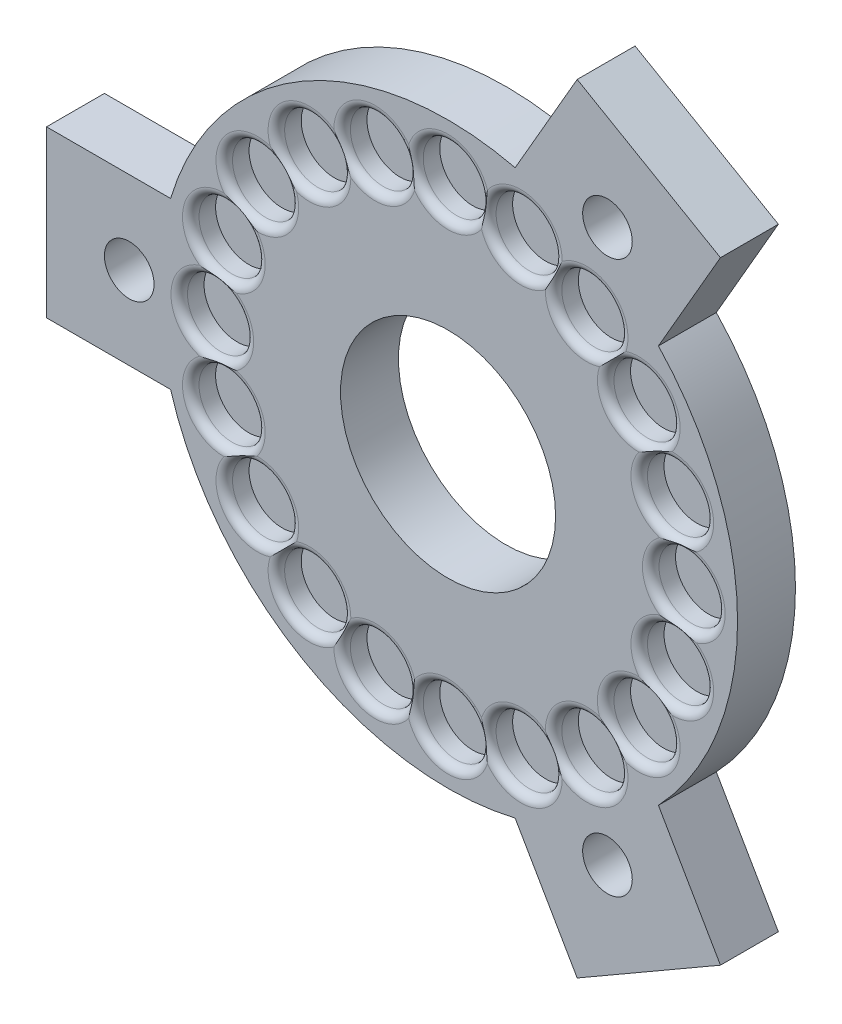
SolidWorks part; units mm, degrees
ref_plane "Ebene vorne" through (0, 0, 0) normal (0, 0, 1) x (1, 0, 0)
ref_plane "Ebene oben" through (0, 0, 0) normal (0, 1, 0) x (1, 0, 0)
ref_plane "Ebene rechts" through (0, 0, 0) normal (1, 0, 0) x (0, 0, -1)
sketch "Skizze1" plane through (0, 0, 0) normal (0, 0, 1) x (1, 0, 0)
  circle A0 centre (0, 0) radius 30.1538
  circle A1 centre (0, 30.1538) radius 4.3077
  circle A2 centre (9.3181, 28.678) radius 4.3077
  circle A3 centre (17.724, 24.395) radius 4.3077
  circle A4 centre (24.395, 17.724) radius 4.3077
  circle A5 centre (28.678, 9.3181) radius 4.3077
  circle A6 centre (30.1538, 0) radius 4.3077
  circle A7 centre (28.678, -9.3181) radius 4.3077
  circle A8 centre (24.395, -17.724) radius 4.3077
  circle A9 centre (17.724, -24.395) radius 4.3077
  circle A10 centre (9.3181, -28.678) radius 4.3077
  circle A11 centre (0, -30.1538) radius 4.3077
  circle A12 centre (-9.3181, -28.678) radius 4.3077
  circle A13 centre (-17.724, -24.395) radius 4.3077
  circle A14 centre (-24.395, -17.724) radius 4.3077
  circle A15 centre (-28.678, -9.3181) radius 4.3077
  circle A16 centre (-30.1538, 0) radius 4.3077
  circle A17 centre (-28.678, 9.3181) radius 4.3077
  circle A18 centre (-24.395, 17.724) radius 4.3077
  circle A19 centre (-17.724, 24.395) radius 4.3077
  circle A20 centre (-9.3181, 28.678) radius 4.3077
  circle A21 centre (0, 0) radius 35
  point P46 (0, 0)
  dimension "D1" = 20
  dimension "D2" = 70
extrude "Aufsatz-Linear austragen3" add sketch "Skizze1" along normal blind 7 contours A21
sketch "Skizze3" plane through (0, 0, 7) normal (0, 0, 1) x (1, 0, 0)
  circle A0 centre (0, 0) radius 28.5
  circle A1 centre (0, 28.5) radius 4
  circle A2 centre (8.807, 27.1051) radius 4
  circle A3 centre (16.7519, 23.057) radius 4
  circle A4 centre (23.057, 16.7519) radius 4
  circle A5 centre (27.1051, 8.807) radius 4
  circle A6 centre (28.5, 0) radius 4
  circle A7 centre (27.1051, -8.807) radius 4
  circle A8 centre (23.057, -16.7519) radius 4
  circle A9 centre (16.7519, -23.057) radius 4
  circle A10 centre (8.807, -27.1051) radius 4
  circle A11 centre (0, -28.5) radius 4
  circle A12 centre (-8.807, -27.1051) radius 4
  circle A13 centre (-16.7519, -23.057) radius 4
  circle A14 centre (-23.057, -16.7519) radius 4
  circle A15 centre (-27.1051, -8.807) radius 4
  circle A16 centre (-28.5, 0) radius 4
  circle A17 centre (-27.1051, 8.807) radius 4
  circle A18 centre (-23.057, 16.7519) radius 4
  circle A19 centre (-16.7519, 23.057) radius 4
  circle A20 centre (-8.807, 27.1051) radius 4
  point P46 (0, 0)
  dimension "D1" = 20
  dimension "D2" = 57
  dimension "D3" = 8
extrude "Schnitt-Linear austragen1" cut sketch "Skizze3" against normal blind 3 contours A0 A8 | A0 A8 | A0 A3 | A0 A3 | A10 | A9 | A7 | A6 | A5 | A4 | A2 | A1 | A20 | A19 | A18 | A17 | A16 | A15 | A14 | A13 | A12 | A11 region at (24.3887, -17.7194, 7) region at (21.6435, -15.7249, 7) region at (15.7249, 21.6435, 7) region at (17.7194, 24.3887, 7)
sketch "Skizze4" plane through (0, 0, 7) normal (0, 0, 1) x (1, 0, 0)
  circle A0 centre (0, 0) radius 13
  dimension "D1" = 26
extrude "Schnitt-Linear austragen2" cut sketch "Skizze4" against normal up to next
ref_plane "Ebene1" through (0, 0, 0) normal (0, 0, -1) x (-1, 0, 0)
sketch "Skizze6" plane through (0, 0, 0) normal (0, 0, -1) x (-1, 0, 0)
  line L0 (-15.6103, -47.0378) -> (-32.9308, -37.0378)
  line L5 (48.541, 10) -> (33.541, 10)
  line L6 (48.541, 10) -> (48.541, -10)
  line L7 (48.541, -10) -> (33.541, -10)
  line L8 (33.541, 10) -> (33.541, -10)
  line L9 (-15.6103, -47.0378) -> (-8.1103, -34.0474)
  line L10 (-8.1103, -34.0474) -> (-25.4308, -24.0474)
  line L11 (-32.9308, -37.0378) -> (-25.4308, -24.0474)
  line L12 (-32.9308, 37.0378) -> (-15.6103, 47.0378)
  line L13 (-32.9308, 37.0378) -> (-25.4308, 24.0474)
  line L14 (-25.4308, 24.0474) -> (-8.1103, 34.0474)
  line L15 (-15.6103, 47.0378) -> (-8.1103, 34.0474)
  circle A0 centre (0, 0) radius 35 construction
  point P18 (0, 0)
  dimension "D1" = 3
  dimension "D3" = 20
  dimension "D4" = 15
  dimension "D5" = 10
extrude "Aufsatz-Linear austragen4" add sketch "Skizze6" against normal blind 7
sketch "Skizze9" plane through (0, 0, 0) normal (0, 0, -1) x (-1, 0, 0)
  line L0 (48.541, -10) -> (48.541, 10) construction
  circle A0 centre (38.541, 0) radius 3
  circle A1 centre (-19.2705, -33.3775) radius 3
  circle A2 centre (-19.2705, 33.3775) radius 3
  point P11 (0, 0)
  dimension "D1" = 10
  dimension "D2" = 3
extrude "Schnitt-Linear austragen5" cut sketch "Skizze9" against normal up to next
fillet "Verrundung1" radius 1 20 edges at (27.057, 16.7519, 7) (20.7519, 23.057, 7) (12.807, 27.1051, 7) (4, 28.5, 7) (-4.807, 27.1051, 7) (-12.7519, 23.057, 7) (-19.057, 16.7519, 7) (-23.1051, 8.807, 7) (-24.5, 0, 7) (-23.1051, -8.807, 7) (-19.057, -16.7519, 7) (-12.7519, -23.057, 7) (-4.807, -27.1051, 7) (4, -28.5, 7) (12.807, -27.1051, 7) (20.7519, -23.057, 7) (27.057, -16.7519, 7) (31.1051, -8.807, 7) (31.1051, 8.807, 7) (32.5, 0, 7)
